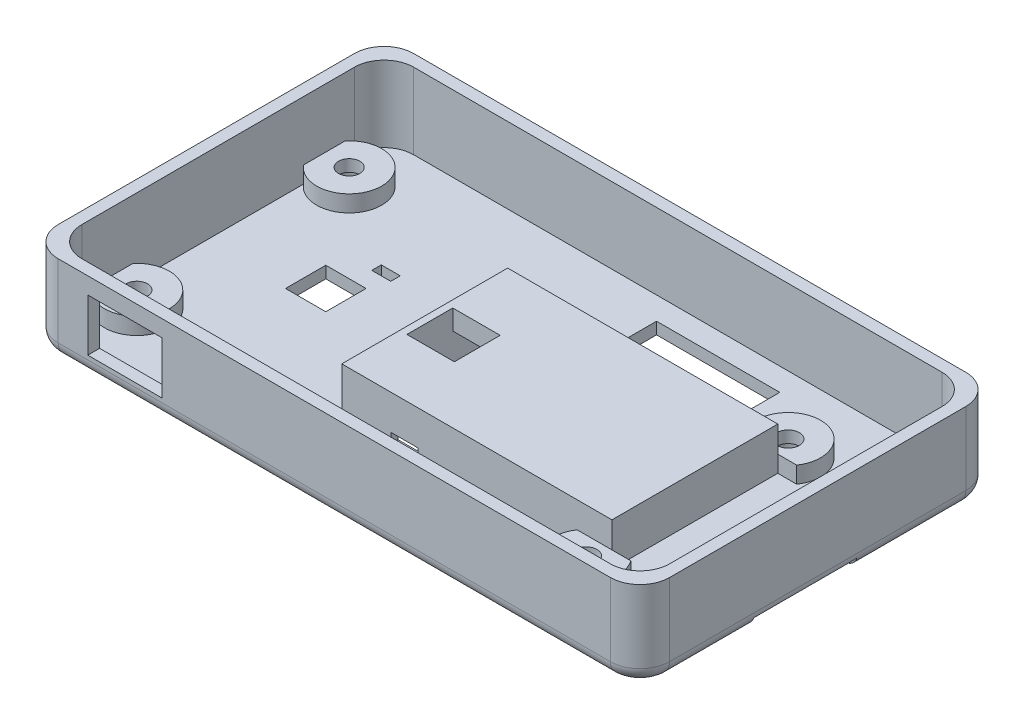
SolidWorks part; units mm, degrees
material "ABS"
ref_plane "Спереди" through (0, 0, 0) normal (0, 0, 1) x (1, 0, 0)
ref_plane "Сверху" through (0, 0, 0) normal (0, 1, 0) x (1, 0, 0)
ref_plane "Справа" through (0, 0, 0) normal (1, 0, 0) x (0, 0, -1)
sketch "Эскиз1" plane through (0, 0, 0) normal (0, 1, 0) x (1, 0, 0)
  line L11 (61.92, -36) -> (-61.92, -36)
  line L12 (61.92, -36) -> (61.92, 36)
  line L13 (61.92, 36) -> (-61.92, 36)
  line L14 (-61.92, -36) -> (-61.92, 36)
  point P0 (0, 0)
extrude "Бобышка-Вытянуть1" add sketch "Эскиз1" along normal blind 17.76
sketch "Эскиз8" plane through (0, 17.76, 0) normal (0, 1, 0) x (1, 0, 0)
  line L7 (-59.52, 33.6) -> (59.52, 33.6)
  line L8 (-59.52, 33.6) -> (-59.52, -33.6)
  line L9 (-59.52, -33.6) -> (59.52, -33.6)
  line L10 (59.52, 33.6) -> (59.52, -33.6)
extrude "Вырез-Вытянуть5" cut sketch "Эскиз8" against normal blind 15.36
sketch "Эскиз10" plane through (0, 2.4, 0) normal (0, 1, 0) x (1, 0, 0)
  line L0 (-61.92, 0) -> (96.256, 0) construction
  line L1 (-61.92, 36) -> (-61.92, -36) construction
  line L3 (39.24, 14.6) -> (39.24, -19)
  line L4 (39.24, -19) -> (-15.48, -19)
  line L5 (-15.48, 14.6) -> (-15.48, -19)
  line L9 (39.24, 14.6) -> (-15.48, 14.6)
sketch "Эскиз11" plane through (0, 0, 33.6) normal (0, 0, 1) x (1, 0, 0)
  line L3 (-49.92, 3.84) -> (-34.92, 3.84)
  line L4 (-49.92, 3.84) -> (-49.92, 14.4)
  line L5 (-49.92, 14.4) -> (-34.92, 14.4)
  line L6 (-34.92, 3.84) -> (-34.92, 14.4)
extrude "Бобышка-Вытянуть2" add sketch "Эскиз10" along normal blind 8.64
extrude "Вырез-Вытянуть7" cut sketch "Эскиз11" along normal blind 5
sketch "Эскиз12" plane through (0, 0, 0) normal (0, -1, 0) x (1, 0, 0)
  line L0 (-59.52, 0) -> (69.6149, 0) construction
  line L2 (37.32, -12.68) -> (37.32, 17.56)
  line L3 (-14.04, 17.56) -> (37.32, 17.56)
  line L4 (-14.04, -12.68) -> (-14.04, 17.56)
  line L9 (-14.04, -12.68) -> (37.32, -12.68)
  point P3 (57.4685, 0)
extrude "Вырез-Вытянуть8" cut sketch "Эскиз12" against normal blind 7
sketch "Эскиз13" plane through (0, 0, 0) normal (0, -1, 0) x (1, 0, 0)
  line L1 (-59.52, 0) -> (-76.8441, 0) construction
  line L8 (37.32, 12.76) -> (61.92, 12.76)
  line L9 (37.32, -8.2) -> (37.32, 12.76)
  line L10 (61.92, -8.2) -> (61.92, 12.76)
  line L11 (61.92, -8.2) -> (37.32, -8.2)
  point P12 (0, 0)
extrude "Вырез-Вытянуть9" cut sketch "Эскиз13" against normal blind 2
sketch "Эскиз21" plane through (0, 7, 0) normal (0, -1, 0) x (1, 0, 0)
  line L1 (0, 0) -> (59.52, 0) construction
  line L8 (-4.44, 7.24) -> (-4.44, -2.04)
  line L9 (-14.04, 7.24) -> (-4.44, 7.24)
  line L10 (-14.04, -2.04) -> (-4.44, -2.04)
  line L11 (-14.04, 2.44) -> (-14.04, 7.24)
  line L12 (-14.04, 2.44) -> (-14.04, -2.04)
extrude "Вырез-Вытянуть16" cut sketch "Эскиз21" against normal through all
sketch "Эскиз14" plane through (0, 0, 0) normal (0, -1, 0) x (1, 0, 0)
  circle A1 centre (-54.48, -21.5) radius 2.16
  circle A3 centre (37.64, -18.3) radius 2.26
  circle A4 centre (37.64, 22.7) radius 2.26
  circle A6 centre (-54.48, 21.5) radius 2.16
  point P4 (0, 0)
sketch "Эскиз22" plane through (0, 0, 0) normal (0, -1, 0) x (1, 0, 0)
  line L0 (-59.52, 0) -> (59.52, 0) construction
  circle A0 centre (37.64, -18.3) radius 3.71
  circle A1 centre (37.64, 22.7) radius 3.71
  circle A4 centre (-54.48, 21.5) radius 3.12
  circle A5 centre (-54.48, -21.5) radius 3.12
fillet "Скругление1" radius 6 4 edges at (-61.92, 8.88, 36) (-61.92, 8.88, -36) (61.92, 8.88, -36) (61.92, 8.88, 36)
fillet "Скругление3" radius 3 8 edges at (60.1626, 0, -34.2426) (0, 0, -36) (-60.1626, 0, -34.2426) (-61.92, 0, 0) (-60.1626, 0, 34.2426) (61.92, 0, 21.38) (60.1626, 0, 34.2426) (0, 0, 36)
fillet "Скругление5" radius 6 4 edges at (-59.52, 10.08, 33.6) (-59.52, 10.08, -33.6) (59.52, 10.08, 33.6) (59.52, 10.08, -33.6) tangent propagation no
sketch "Эскиз19" plane through (0, 0, 17.56) normal (0, 0, -1) x (-1, 0, 0)
  line L4 (5.5, 2) -> (0, 2)
  line L5 (5.5, 2) -> (5.5, 4)
  line L6 (5.5, 4) -> (0, 4)
  line L7 (0, 2) -> (0, 4)
extrude "Вырез-Вытянуть14" cut sketch "Эскиз19" against normal blind 3.84
sketch "Эскиз20" plane through (0, 0, -12.68) normal (0, 0, 1) x (1, 0, 0)
  line L4 (-5.5, 2) -> (0, 2)
  line L5 (-5.5, 2) -> (-5.5, 4)
  line L6 (-5.5, 4) -> (0, 4)
  line L7 (0, 2) -> (0, 4)
extrude "Вырез-Вытянуть15" cut sketch "Эскиз20" against normal blind 3.84
sketch "Эскиз23" plane through (0, 2.4, 0) normal (0, 1, 0) x (1, 0, 0)
  line L1 (-59.52, 25.7302) -> (-59.52, 17.2698)
  line L3 (-59.52, 27.6) -> (-59.52, -27.6) construction
  line L4 (-59.52, -25.7302) -> (-59.52, -17.2698)
  arc A0 (-59.52, 17.2698) -> (-59.52, 25.7302) centre (-54.48, 21.5) ccw
  arc A2 (-59.52, -25.7302) -> (-59.52, -17.2698) centre (-54.48, -21.5) ccw
sketch "Эскиз24" plane through (0, 2.4, 0) normal (0, 1, 0) x (1, 0, 0)
  line L3 (-59.52, 0) -> (71.623, 0) construction
  line L6 (32.1988, -19) -> (43.0812, -19)
  line L7 (32.1988, 14.6) -> (43.0759, 14.5923)
  arc A2 (32.1988, -19) -> (43.0812, -19) centre (37.64, -22.7) ccw
  arc A3 (32.1988, 14.6) -> (43.0759, 14.5923) centre (37.64, 18.3) cw
extrude "Бобышка-Вытянуть3" add sketch "Эскиз24" along normal blind 3.36
extrude "Бобышка-Вытянуть4" add sketch "Эскиз23" along normal blind 3.36
sketch "Эскиз25" plane through (0, 0, 0) normal (0, 1, 0) x (1, 0, 0)
  line L0 (-59.52, 0) -> (57.2984, 0) construction
  circle A0 centre (-54.48, -21.5) radius 2.16
  circle A1 centre (-54.48, 21.5) radius 2.16
  circle A4 centre (37.64, 18.3) radius 2.26
  circle A5 centre (37.64, -22.7) radius 2.26
extrude "Вырез-Вытянуть17" cut sketch "Эскиз25" along normal through all
extrude "Вырез-Вытянуть18" cut sketch "Эскиз22" against normal blind 3.36
sketch "Эскиз26" plane through (0, 0, 0) normal (0, -1, 0) x (1, 0, 0)
  line L0 (-59.52, 0) -> (71.8908, 0) construction
  line L2 (0.2816, -17.96) -> (0.2816, -29)
  line L7 (25.2416, -29) -> (0.2816, -29)
  line L8 (-33.64, -11) -> (-37.48, -11)
  line L9 (-34.88, 2.84) -> (-43.04, 2.84)
  line L10 (-34.88, 2.84) -> (-34.88, -5.32)
  line L11 (-34.88, -5.32) -> (-43.04, -5.32)
  line L12 (-43.04, 2.84) -> (-43.04, -5.32)
  line L13 (-37.48, -11) -> (-37.48, -9.08)
  line L14 (-37.48, -9.08) -> (-33.64, -9.08)
  line L15 (-33.64, -9.08) -> (-33.64, -11)
  line L16 (25.2416, -17.96) -> (25.2416, -29)
  line L17 (25.2416, -17.96) -> (0.2816, -17.96)
extrude "Вырез-Вытянуть19" cut sketch "Эскиз26" against normal through all
